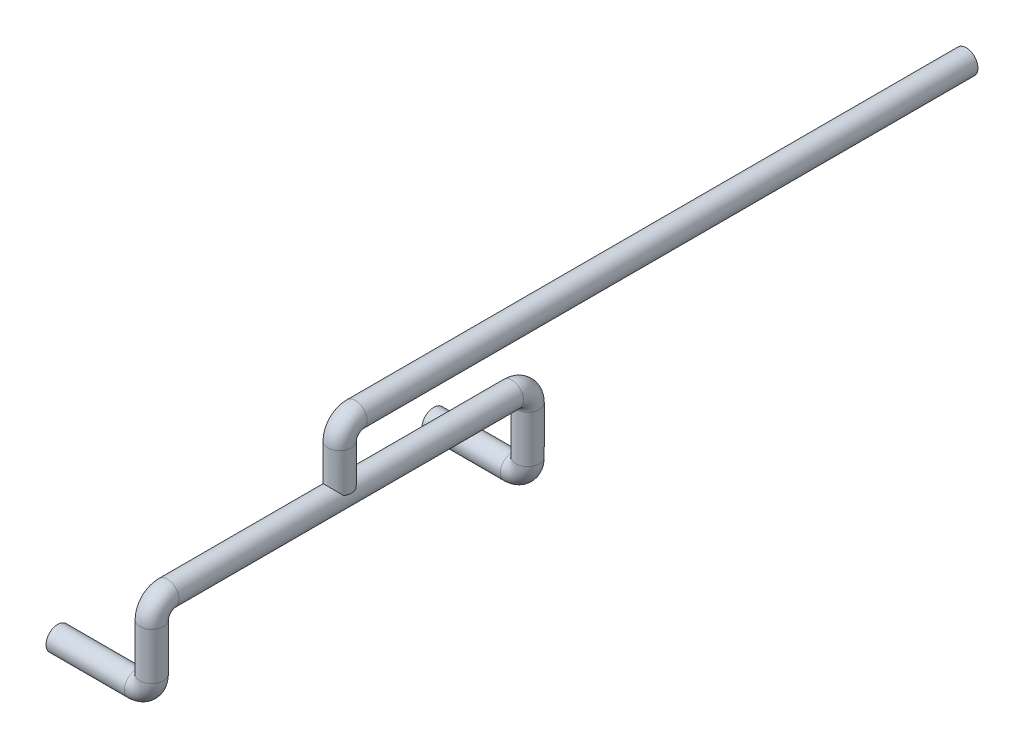
SolidWorks part; units mm, degrees
material "ABS PC"
ref_plane "Front Plane" through (0, 0, 0) normal (0, 0, 1) x (1, 0, 0)
ref_plane "Top Plane" through (0, 0, 0) normal (0, 1, 0) x (1, 0, 0)
ref_plane "Right Plane" through (0, 0, 0) normal (1, 0, 0) x (0, 0, -1)
sketch3d "3DSketch1"
  line L0 (0, 0, 0) -> (0, 0, 110)
  line L1 (0, -10, 120) -> (0, -40, 120)
  line L2 (-10, -50, 120) -> (-60, -50, 120)
  line L3 (0, 0, 0) -> (0, 0, -110)
  line L4 (0, -10, -120) -> (0, -40, -120)
  line L5 (-10, -50, -120) -> (-60, -50, -120)
  arc A0 (0, -40, -120) -> (-10, -50, -120) centre (-10, -40, -120) ccw
  arc A1 (0, -10, -120) -> (0, 0, -110) centre (0, -10, -110) ccw
  arc A2 (0, -10, 120) -> (0, 0, 110) centre (0, -10, 110) ccw
  arc A3 (-10, -50, 120) -> (0, -40, 120) centre (-10, -40, 120) ccw
  point P10 (0, -50, -120)
  point P11 (-10, -40, -130)
  point P14 (0, 0, -120)
  point P15 (10, -10, -110)
  point P18 (0, 0, 120)
  point P19 (-10, -10, 110)
  point P22 (0, -50, 120)
  point P23 (-10, -40, 130)
  dimension "D4" = 10
  dimension "D1" = 60
  dimension "D2" = 50
  dimension "D3" = 240
sweep "Sweep1" add path "3DSketch1" circular profile diameter 15 parameters "D3"=15
sketch "Sketch30" plane through (0, 0, 0) normal (1, 0, 0) x (0, 0, -1)
  line L0 (0, 3.789) -> (0, 28.789)
  line L2 (10, 38.789) -> (400, 38.789)
  arc A0 (0, 28.789) -> (10, 38.789) centre (10, 28.789) cw
  point P2 (0, 0)
  point P3 (0, 7.5)
  point P7 (0, 38.789)
  point P8 (0, 0)
  point P9 (0, 5.5686)
  point P10 (0, 6.226)
  point P11 (0, 0)
  point P12 (0, 4.2728)
  point P13 (0, 3.789)
  dimension "D3" = 10
  dimension "D1" = 35
  dimension "D2" = 400
sweep "Sweep2" add path "Sketch30" circular profile diameter 15 parameters "D3"=15
sweep "Cut-Sweep1" cut path "3DSketch1<2>" circular profile diameter 12.5 parameters "D3"=12.5
sketch3d "3DSketch1<2>" same geometry as "3DSketch1"
sweep "Cut-Sweep2" cut path "Sketch30<2>" circular profile diameter 12.5 parameters "D3"=12.5
sketch "Sketch30<2>" plane through (0, 0, 0) normal (1, 0, 0) x (0, 0, -1) same geometry as "Sketch30"
